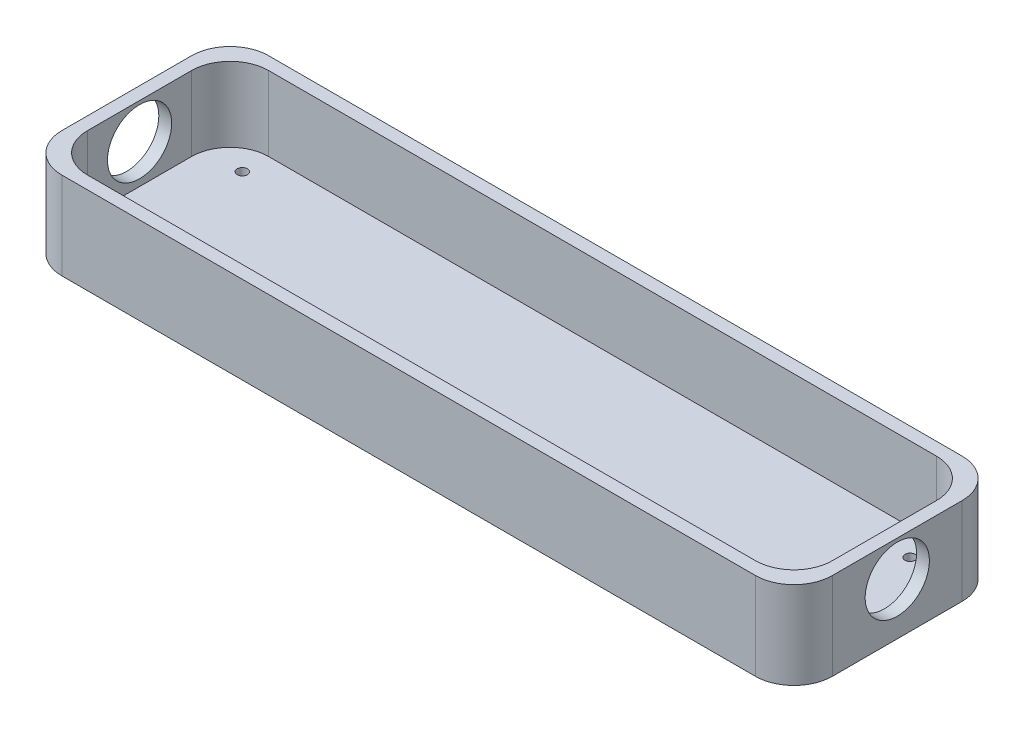
SolidWorks part; units mm, degrees
material "ABS"
ref_plane "Front Plane" through (0, 0, 0) normal (0, 0, 1) x (1, 0, 0)
ref_plane "Top Plane" through (0, 0, 0) normal (0, 1, 0) x (1, 0, 0)
ref_plane "Right Plane" through (0, 0, 0) normal (1, 0, 0) x (0, 0, -1)
sketch "Sketch1" plane through (0, 0, 0) normal (0, 1, 0) x (1, 0, 0)
  line L0 (-150, -40.25) -> (150, -40.25)
  line L1 (-150, -40.25) -> (-150, 40.25)
  line L2 (150, -40.25) -> (150, 40.25)
  line L3 (-150, 40.25) -> (150, 40.25)
  line L4 (-150, -40.25) -> (150, 40.25) construction
  line L5 (150, -40.25) -> (-150, 40.25) construction
  line L10 (-145, -35.25) -> (-145, 35.25)
  line L11 (-145, 35.25) -> (145, 35.25)
  line L12 (145, -35.25) -> (145, 35.25)
  line L13 (-145, -35.25) -> (145, -35.25)
  point P1 (0, 0)
  dimension "D1" = 300
  dimension "D2" = 80.5
  dimension "D3" = 5
extrude "Boss-Extrude1" add sketch "Sketch1" along normal blind 34
extrude "Boss-Extrude2" add sketch "Sketch1<3>" along normal blind 5 contours L10 L13 L12 L11 region at (0, 0, 0)
sketch "Sketch1<3>" plane through (0, 0, 0) normal (0, 1, 0) x (1, 0, 0) same geometry as "Sketch1"
fillet "Fillet1" radius 15 1 edges at (-150, 17, 40.25) type face fillet first side face at (0, 17, 40.25) second side face at (-150, 17, 0)
fillet "Fillet2" radius 15 1 edges at (-150, 17, -40.25) type face fillet first side face at (-150, 17, -7.5) second side face at (0, 17, -40.25)
fillet "Fillet3" radius 15 1 edges at (150, 17, -40.25) type face fillet first side face at (7.5, 17, -40.25) second side face at (150, 17, 0)
fillet "Fillet4" radius 15 1 edges at (150, 17, 40.25) type face fillet first side face at (150, 17, 7.5) second side face at (7.5, 17, 40.25)
fillet "Fillet5" radius 15 1 edges at (-145, 19.5, -35.25) type face fillet first side face at (0, 19.5, -35.25) second side face at (-145, 19.5, 0)
fillet "Fillet6" radius 15 1 edges at (-145, 19.5, 35.25) type face fillet first side face at (0, 19.5, 35.25) second side face at (-145, 19.5, 7.5)
fillet "Fillet7" radius 15 1 edges at (145, 19.5, -35.25) type face fillet first side face at (7.5, 19.5, -35.25) second side face at (145, 19.5, 0)
fillet "Fillet8" radius 15 1 edges at (145, 19.5, 35.25) type face fillet first side face at (145, 19.5, 7.5) second side face at (7.5, 19.5, 35.25)
sketch "Sketch2" plane through (0, 0, 0) normal (0, -1, 0) x (-1, 0, 0)
  line L0 (-150, 0) -> (-130, 0)
  line L1 (-150, -25.25) -> (-150, 25.25) construction
  line L2 (-130, 0) -> (-130, -25)
  circle A1 centre (-130, -25) radius 2
  dimension "D3" = 4
  dimension "D1" = 20
  dimension "D2" = 25
extrude "Cut-Extrude1" cut sketch "Sketch2" against normal through all contours A1
mirror "Mirror1" about plane through (0, 0, 0) normal (0, 0, 1) of "Cut-Extrude1"
mirror "Mirror2" about plane through (0, 0, 0) normal (1, 0, 0) of "Mirror1", "Cut-Extrude1"
sketch "Sketch3" plane through (150, 0, 0) normal (1, 0, 0) x (0, 0, -1)
  line L0 (0, 34) -> (0, 6.25)
  line L1 (-25.25, 34) -> (25.25, 34) construction
  circle A0 centre (0, 20.125) radius 12.5
  dimension "D2" = 25
  dimension "D1" = 27.75
extrude "Cut-Extrude2" cut sketch "Sketch3" against normal through all contours A0
